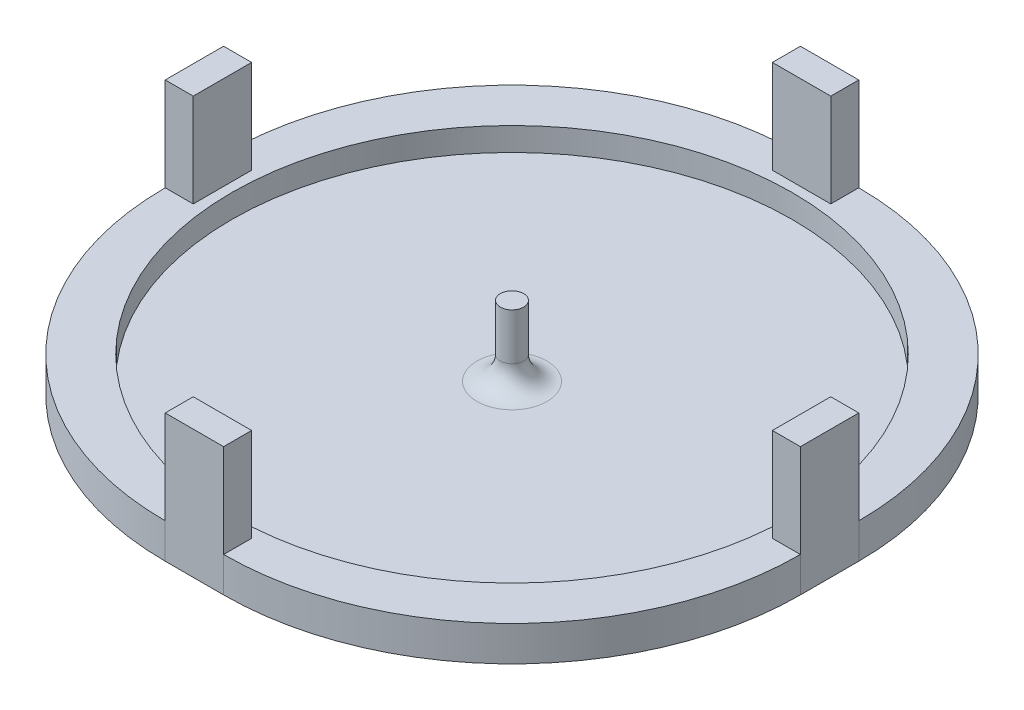
SolidWorks part; units mm, degrees
note: The reader was unsure of these and kept them because the rebuilt part matched: shared geometry of "Sketch1<4>", "Sketch1<5>".
ref_plane "Front Plane" through (0, 0, 0) normal (0, 0, 1) x (1, 0, 0)
ref_plane "Top Plane" through (0, 0, 0) normal (0, 1, 0) x (1, 0, 0)
ref_plane "Right Plane" through (0, 0, 0) normal (1, 0, 0) x (0, 0, -1)
sketch "Sketch1" plane through (0, 0, 0) normal (0, 1, 0) x (1, 0, 0)
  line L0 (-13.6, -1.25) -> (13.6, -1.25)
  line L1 (-13.6, -1.25) -> (-13.6, 1.25)
  line L2 (-13.6, 1.25) -> (13.6, 1.25)
  line L3 (13.6, -1.25) -> (13.6, 1.25)
  line L4 (-13.6, -1.25) -> (13.6, 1.25) construction
  line L5 (-13.6, 1.25) -> (13.6, -1.25) construction
  line L6 (-1.25, 13.6) -> (1.25, 13.6)
  line L7 (-1.25, 13.6) -> (-1.25, -13.6)
  line L8 (-1.25, -13.6) -> (1.25, -13.6)
  line L9 (1.25, 13.6) -> (1.25, -13.6)
  line L10 (13.6, 1.25) -> (13.6, -1.25)
  line L11 (13.6, 1.25) -> (-13.6, 1.25)
  line L12 (-13.6, 1.25) -> (-13.6, -1.25)
  line L13 (13.6, -1.25) -> (-13.6, -1.25)
  line L14 (1.25, -13.6) -> (-1.25, -13.6)
  line L15 (1.25, -13.6) -> (1.25, 13.6)
  line L16 (1.25, 13.6) -> (-1.25, 13.6)
  line L17 (-1.25, -13.6) -> (-1.25, 13.6)
  line L18 (0, -55) -> (0, 55) construction
  line L19 (-55, 0) -> (55, 0) construction
  line L20 (13.6, -1.25) -> (12.4, -1.25)
  line L21 (1.25, 13.6) -> (-1.25, 13.6)
  line L22 (1.25, 13.6) -> (1.25, 12.4)
  line L23 (1.25, 12.4) -> (-1.25, 12.4)
  line L24 (-1.25, 13.6) -> (-1.25, 12.4)
  line L25 (13.6, -1.25) -> (13.6, 1.25)
  line L26 (13.6, 1.25) -> (12.4, 1.25)
  line L27 (12.4, -1.25) -> (12.4, 1.25)
  line L28 (-1.25, -13.6) -> (-1.25, -12.4)
  line L29 (-1.25, -13.6) -> (1.25, -13.6)
  line L30 (1.25, -13.6) -> (1.25, -12.4)
  line L31 (-1.25, -12.4) -> (1.25, -12.4)
  line L32 (-13.6, 1.25) -> (-12.4, 1.25)
  line L33 (-13.6, 1.25) -> (-13.6, -1.25)
  line L34 (-13.6, -1.25) -> (-12.4, -1.25)
  line L35 (-12.4, 1.25) -> (-12.4, -1.25)
  arc A1 (-13.6, 1.25) -> (-1.25, 13.6) centre (-1.25, 1.25) cw
  arc A2 (1.25, 13.6) -> (13.6, 1.25) centre (1.25, 1.25) cw
  arc A3 (13.6, -1.25) -> (1.25, -13.6) centre (1.25, -1.25) cw
  arc A4 (-13.6, -1.25) -> (-1.25, -13.6) centre (-1.25, -1.25) ccw
  circle A5 centre (0, 0) radius 12
  point P18 (0, 0)
  point P41 (0, 0)
  dimension "D2" = 0
  dimension "D1" = 27.2
  dimension "D3" = 2.5
  dimension "D4" = 1.25
  dimension "D5" = 13.6
  dimension "D6" = 13.6
  dimension "D7" = 27.2
  dimension "D8" = 1.2
  dimension "D9" = 4
extrude "Boss-Extrude1" add sketch "Sketch1" along normal blind 5.5 contours L35 L2 L1 L0 | L23 L9 L6 L7 | L27 L13 L3 L11 | L31 L17 L8 L15
extrude "Boss-Extrude2" add sketch "Sketch1<4>" along normal blind 0.5 separate body contours L7 A5 L2 | L2 A5 L9 | L9 A5 L7 L2 | L2 A5 L0 L7 | L9 L2 L7 L0 | L0 A5 L2 L9 | L9 A5 L0 | L0 A5 L7 | L7 A5 L9 L0
sketch "Sketch1<4>" plane through (0, 0, 0) normal (0, 1, 0) x (1, 0, 0) same geometry as "Sketch1"
extrude "Boss-Extrude3" add sketch "Sketch1<5>" along normal blind 1.5 contours A5 L17 L7 A1 L2 L11 | A5 L11 A2 L9 L15 | A5 L15 L23 L17 | A5 L15 A3 L13 | A5 L13 L27 L11 | A5 L13 L0 A4 L17 | A5 L11 L35 L13 | A5 L17 L31 L15
sketch "Sketch1<5>" plane through (0, 0, 0) normal (0, 1, 0) x (1, 0, 0) same geometry as "Sketch1"
sketch "Sketch2" plane through (0, 0.5, 0) normal (0, 1, 0) x (1, 0, 0)
  circle A0 centre (0, 0) radius 0.5
extrude "Boss-Extrude4" add sketch "Sketch2" along normal blind 3
fillet "Fillet1" radius 1 1 edges at (0, 0.5, 0.5)
